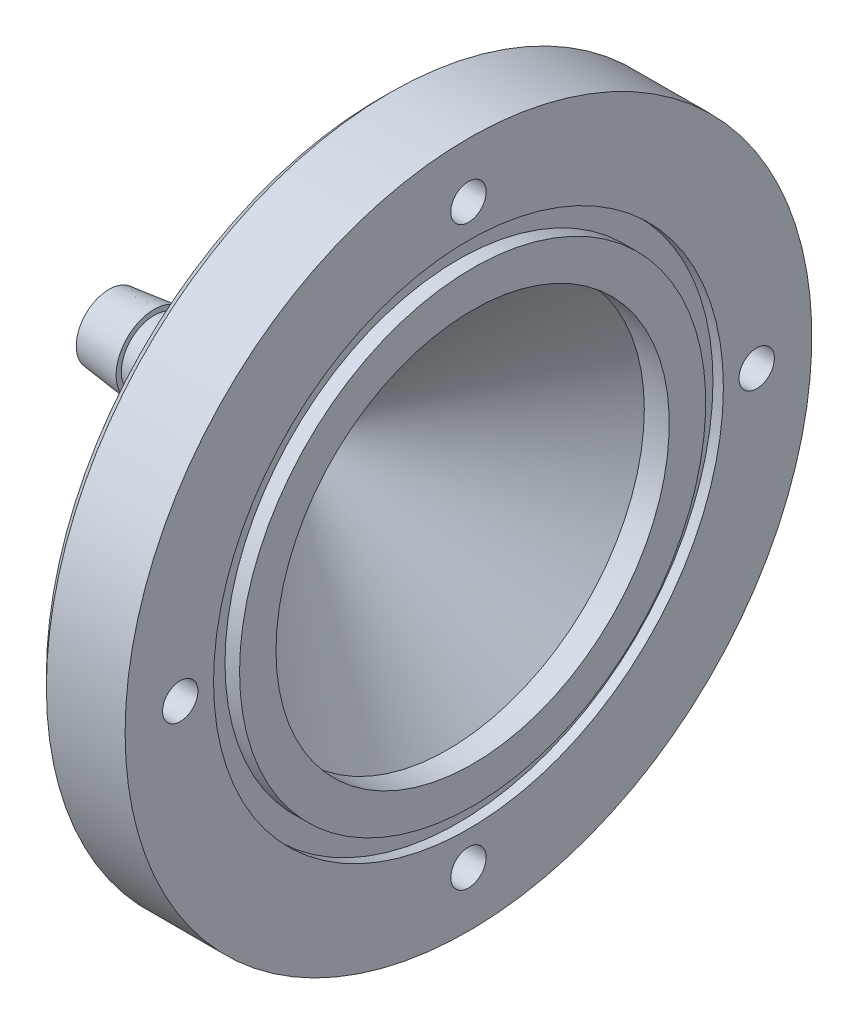
SolidWorks part; units mm, degrees
ref_plane "Front Plane" through (0, 0, 0) normal (0, 0, 1) x (1, 0, 0)
ref_plane "Top Plane" through (0, 0, 0) normal (0, 1, 0) x (1, 0, 0)
ref_plane "Right Plane" through (0, 0, 0) normal (1, 0, 0) x (0, 0, -1)
sketch "Sketch1" plane through (0, 0, 0) normal (0, 0, 1) x (1, 0, 0)
  line L0 (-801.9206, 0) -> (36107.5283, 0) construction
  line L3 (-13.7431, 3.65) -> (-13.7431, 3.15)
  line L8 (-18.0764, 1.9) -> (0, 1.9)
  line L9 (-18.0764, 1.9) -> (-18.0764, 3.15)
  line L10 (16.4699, 24.5) -> (16.4699, 33)
  line L12 (16.4699, 33) -> (7.9039, 33)
  line L16 (16.4699, 24.5) -> (15.4699, 24.5)
  line L17 (15.4699, 24.5) -> (15.4699, 18.9)
  line L18 (7.9039, 33) -> (7.9039, 18.9)
  line L20 (0, 1.9) -> (14.4699, 18.9)
  line L21 (-18.0764, 3.15) -> (-13.7431, 3.65)
  line L22 (14.4699, 18.9) -> (15.4699, 18.9)
  line L23 (-13.7431, 3.15) -> (-9.4098, 3.65)
  line L25 (-9.4098, 3.15) -> (-5.0764, 3.65)
  line L26 (-9.4098, 3.65) -> (-9.4098, 3.15)
  line L27 (-5.0764, 3.65) -> (7.9039, 18.9)
  line L33 (15.4699, 22.4) -> (16.8699, 22.4)
  line L34 (16.8699, 22.4) -> (16.8699, 18.9)
  line L35 (16.8699, 18.9) -> (15.4699, 18.9)
  point P3 (0, 0)
  point P10 (0, 0)
  dimension "D3" = 1
  dimension "D2" = 7.3
  dimension "D6" = 3.8
  dimension "D7" = 6.3
  dimension "D5" = 33
  dimension "D8" = 24.5
  dimension "D4" = 5
  dimension "D9" = 1
  dimension "D11" = 13
  dimension "D12" = 8.566
  dimension "D16" = 3.5
  dimension "D10" = 2.1
  dimension "D13" = 0.4
revolve "Revolve17" add sketch "Sketch1" angle 360 about L0 region at (6.5613, 17.2334, 0) region at (16.1699, 20.65, 0)
sketch "Sketch4" plane through (7.9039, 0, 0) normal (-1, 0, 0) x (0, 0, 1)
  line L0 (0, 18.9) -> (0, 33) construction
  circle A0 centre (0, 0) radius 27.7 construction
  circle A1 centre (0, 0) radius 18.9 construction
  circle A2 centre (0, 0) radius 33 construction
  point P3 (0, 27.7)
  point P7 (27.7, 0)
  point P12 (-27.7, 0)
  point P13 (0, -27.7)
  dimension "D1" = 5.3
  dimension "D2" = 5.3
hole_wizard "CBORE for M3 Hex Socket Head Cap Screw2" positions "Sketch4" profile "Sketch5" counterbore size "M3" standard "ISO"
sketch "Sketch5" plane through (7.9039, -27.7, 0) normal (0, 1, 0) x (0, 0, 1)
  line L0 (0, 0) -> (0, 9.5875)
  line L1 (0, 9.5875) -> (1.7, 8.566)
  line L2 (1.7, 8.566) -> (1.7, 3.4)
  line L3 (1.7, 3.4) -> (3.25, 3.4)
  line L4 (3.25, 3.4) -> (3.25, 0)
  line L5 (3.25, 0) -> (0, 0)
  line L10 (0, 9.5875) -> (-1.7, 8.566) construction
  line L11 (0, -6.35) -> (0, 107.95) construction
  dimension "Hole Dia." = 3.4
  dimension "Hole Depth" = 8.566
  dimension "C'Bore Dia." = 6.5
  dimension "C'Bore Depth" = 3.4
  dimension "Drill Angle" = 118
chamfer "Chamfer1" distance 1 angle 45 1 edges at (7.9039, 0, 33)
sketch "Sketch6" plane through (16.4699, 0, 0) normal (1, 0, 0) x (0, 0, -1)
  line L0 (0, 33) -> (0, 24.5)
  circle A0 centre (0, 0) radius 33
  circle A1 centre (0, 0) radius 33 construction
  circle A2 centre (0, 0) radius 24.5 construction
equation "\"D9@Sketch1\"=\"D3@Sketch1\""
